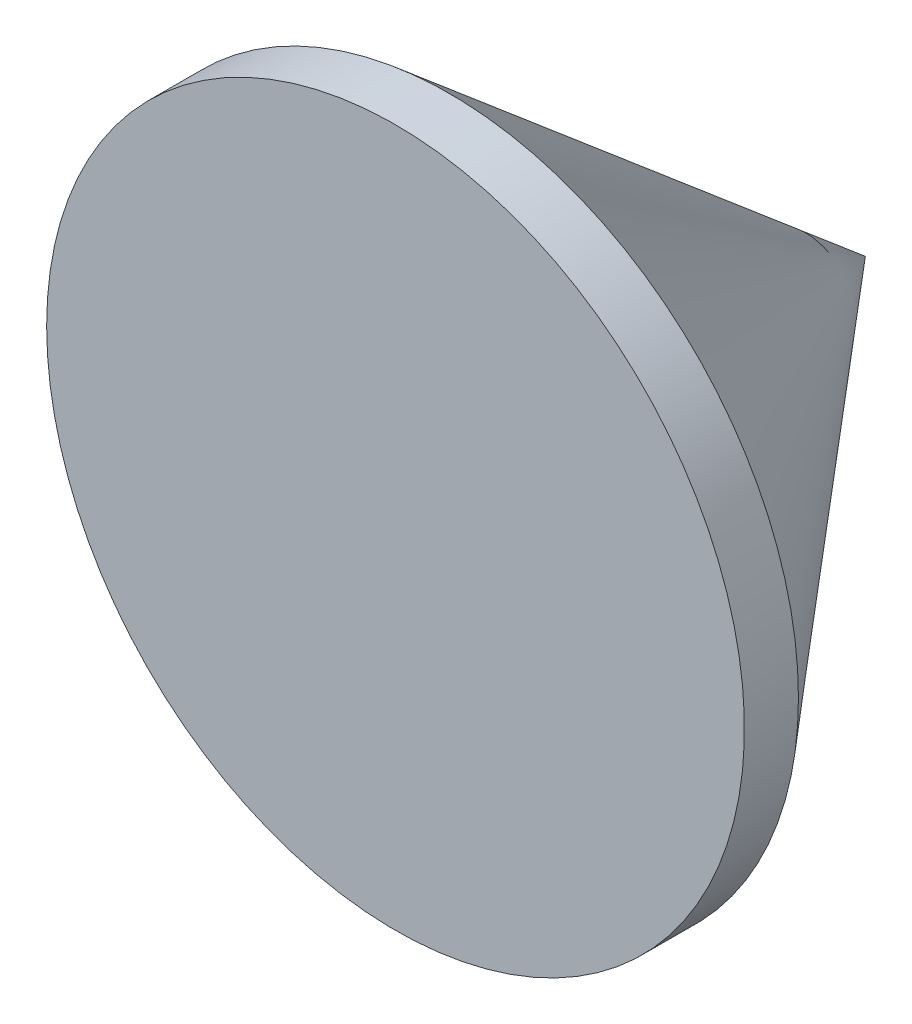
SolidWorks part; units mm, degrees
material "Rockwool"
ref_plane "Front Plane" through (0, 0, 0) normal (0, 0, 1) x (1, 0, 0)
ref_plane "Top Plane" through (0, 0, 0) normal (0, 1, 0) x (1, 0, 0)
ref_plane "Right Plane" through (0, 0, 0) normal (1, 0, 0) x (0, 0, -1)
sketch "Sketch2" plane through (0, 0, 0) normal (0, 1, 0) x (1, 0, 0)
  line L0 (323, 0) -> (323, 50)
  line L2 (323, 50) -> (0, 434.9364)
  line L3 (0, 434.9364) -> (0, 0)
  line L4 (0, 0) -> (323, 0)
  dimension "D1" = 323
  dimension "D2" = 50
  dimension "D3" = 40
revolve "Revolve1" add sketch "Sketch2" angle 360 about L3
sketch "Bend-Lines1" [suppressed] plane through (0, 0, 0) normal (0, 1, 0) x (1, 0, 0)
sketch "Bounding-Box1" [suppressed] plane through (0, 0, 0) normal (0, 1, 0) x (1, 0, 0)
